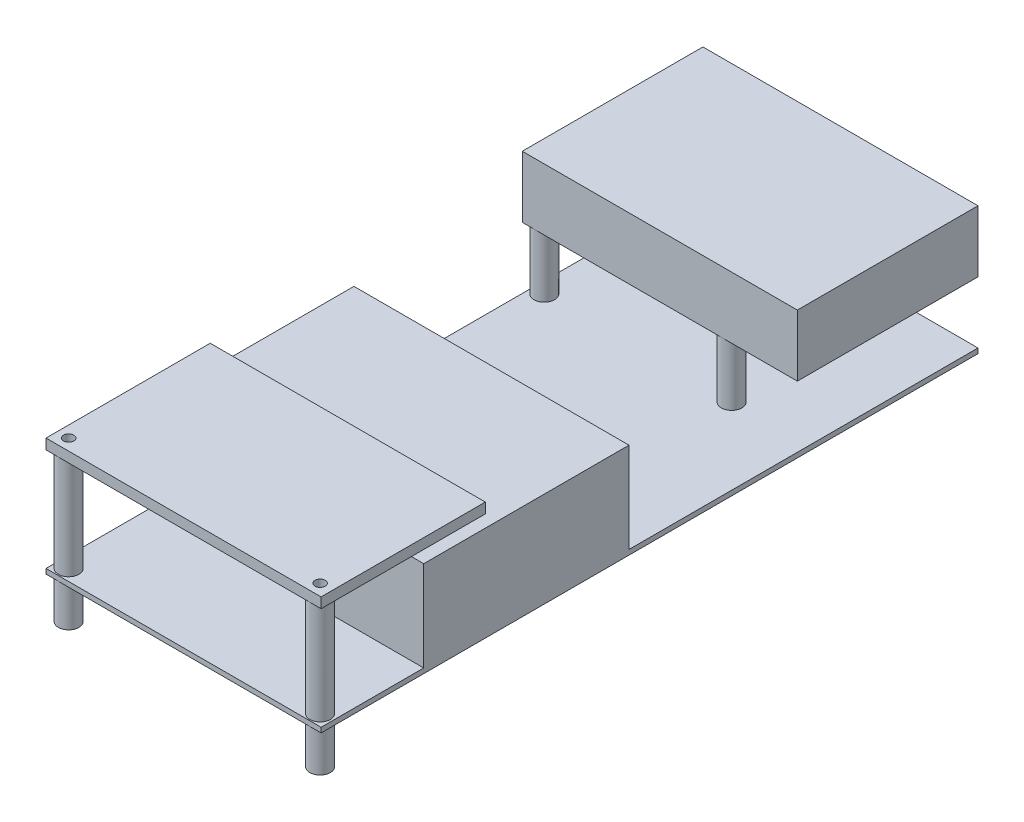
SolidWorks part; units mm, degrees
ref_plane "Front Plane" through (0, 0, 0) normal (0, 0, 1) x (1, 0, 0)
ref_plane "Top Plane" through (0, 0, 0) normal (0, 1, 0) x (1, 0, 0)
ref_plane "Right Plane" through (0, 0, 0) normal (1, 0, 0) x (0, 0, -1)
sketch "Sketch1" plane through (0, 0, 0) normal (0, 1, 0) x (1, 0, 0)
  line L1 (0, 0) -> (85.09, 0)
  line L2 (0, 0) -> (0, 203.2)
  line L3 (0, 203.2) -> (85.09, 203.2)
  line L4 (85.09, 0) -> (85.09, 203.2)
  dimension "D1" = 85.09
  dimension "D2" = 203.2
extrude "Boss-Extrude1" add sketch "Sketch1" along normal blind 1.524
sketch "Sketch2" plane through (0, 1.524, 0) normal (0, 1, 0) x (1, 0, 0)
  line L0 (0, 203.2) -> (0, 0) construction
  line L1 (0, 0) -> (85.09, 0) construction
  circle A0 centre (3.5052, 3.5052) radius 1.5875
  circle A1 centre (81.28, 3.5052) radius 1.5875
  circle A2 centre (3.5052, 199.644) radius 1.5875
  circle A3 centre (3.5052, 150.622) radius 1.5875
  circle A4 centre (61.468, 150.622) radius 1.5875
  circle A5 centre (61.468, 199.644) radius 1.5875
  dimension "D1" = 3.175
  dimension "D2" = 3.5052
  dimension "D3" = 3.5052
  dimension "D4" = 81.28
  dimension "D5" = 150.622
  dimension "D6" = 199.644
  dimension "D7" = 61.468
extrude "Cut-Extrude1" cut sketch "Sketch2" against normal through all
sketch "Sketch3" plane through (0, 1.524, 0) normal (0, 1, 0) x (1, 0, 0)
  line L0 (0, 203.2) -> (0, 0) construction
  line L1 (0, 31.75) -> (85.09, 31.75)
  line L2 (0, 31.75) -> (0, 95.25)
  line L3 (0, 95.25) -> (85.09, 95.25)
  line L4 (85.09, 31.75) -> (85.09, 95.25)
  line L5 (85.09, 0) -> (85.09, 203.2) construction
  line L6 (0, 0) -> (85.09, 0) construction
  dimension "D1" = 31.75
  dimension "D2" = 95.25
extrude "Boss-Extrude2" add sketch "Sketch3" along normal blind 27.94
sketch "Sketch4" plane through (0, 1.524, 0) normal (0, 1, 0) x (1, 0, 0)
  circle A0 centre (3.5052, 199.644) radius 3.175
  circle A1 centre (61.468, 199.644) radius 3.175
  circle A2 centre (3.5052, 150.622) radius 3.175
  circle A3 centre (61.468, 150.622) radius 3.175
  dimension "D1" = 6.35
extrude "Boss-Extrude3" add sketch "Sketch4" along normal blind 19.05
sketch "Sketch5" plane through (0, 20.574, 0) normal (0, 1, 0) x (1, 0, 0)
  line L1 (0, 147.32) -> (85.09, 147.32)
  line L2 (0, 147.32) -> (0, 203.2)
  line L3 (0, 203.2) -> (85.09, 203.2)
  line L4 (0, 95.25) -> (85.09, 95.25)
  line L5 (85.09, 95.25) -> (85.09, 203.2)
  line L6 (85.09, 203.2) -> (0, 203.2)
  line L7 (0, 203.2) -> (0, 95.25)
  line L8 (0, 95.25) -> (85.09, 95.25)
  line L9 (85.09, 95.25) -> (85.09, 203.2)
  line L10 (85.09, 203.2) -> (0, 203.2)
  line L11 (0, 203.2) -> (0, 95.25)
  line L12 (85.09, 147.32) -> (85.09, 203.2)
  circle A1 centre (3.5052, 199.644) radius 3.175
  circle A2 centre (3.5052, 199.644) radius 3.175
  circle M8 centre (3.5052, 199.644) radius 3.175
  dimension "D3" = 55.88
  dimension "D1" = 0
  dimension "D2" = 0
extrude "Boss-Extrude4" add sketch "Sketch5" along normal blind 19.05 contours L1 L9 L3 L2 M8 | M8 region at (42.8068, 20.574, -175.0965) region at (3.5052, 20.574, -199.644)
sketch "Sketch6" plane through (0, 0, 0) normal (0, -1, 0) x (1, 0, 0)
  circle A0 centre (3.5052, -3.5052) radius 3.175
  circle A1 centre (81.28, -3.5052) radius 3.175
  circle A2 centre (61.468, -150.622) radius 3.175
  circle A3 centre (3.5052, -150.622) radius 3.175
  circle A4 centre (3.5052, -199.644) radius 3.175
  circle A5 centre (61.468, -199.644) radius 3.175
  dimension "D1" = 6.35
extrude "Boss-Extrude5" add sketch "Sketch6" along normal blind 12.7
sketch "Sketch7" plane through (0, 1.524, 0) normal (0, 1, 0) x (1, 0, 0)
  circle A0 centre (3.5052, 3.5052) radius 3.175
  circle A1 centre (81.28, 3.5052) radius 3.175
  dimension "D1" = 6.35
extrude "Boss-Extrude6" add sketch "Sketch7" along normal blind 31.75 contours A0 | A1
sketch "Sketch8" plane through (0, 33.274, 0) normal (0, 1, 0) x (1, 0, 0)
  line L0 (85.09, 31.75) -> (85.09, 95.25) construction
  line L1 (0, 0) -> (85.09, 0)
  line L2 (0, 0) -> (0, 50.8)
  line L3 (0, 50.8) -> (85.09, 50.8)
  line L4 (85.09, 0) -> (85.09, 50.8)
  circle A0 centre (3.5052, 3.5052) radius 1.5875
  circle A1 centre (3.5052, 3.5052) radius 3.175
  circle A2 centre (3.5052, 3.5052) radius 3.175
  circle A3 centre (81.28, 3.5052) radius 1.5875
  circle M3 centre (3.5052, 3.5052) radius 3.175
  dimension "D3" = 3.175
  dimension "D2" = 50.8
  dimension "D1" = 0
extrude "Boss-Extrude7" add sketch "Sketch8" along normal blind 3.175 contours L1 L4 L3 L2 A3 M3 | A0 M3 region at (42.7621, 33.274, -25.6024) region at (0.42, 33.274, -3.5052)
